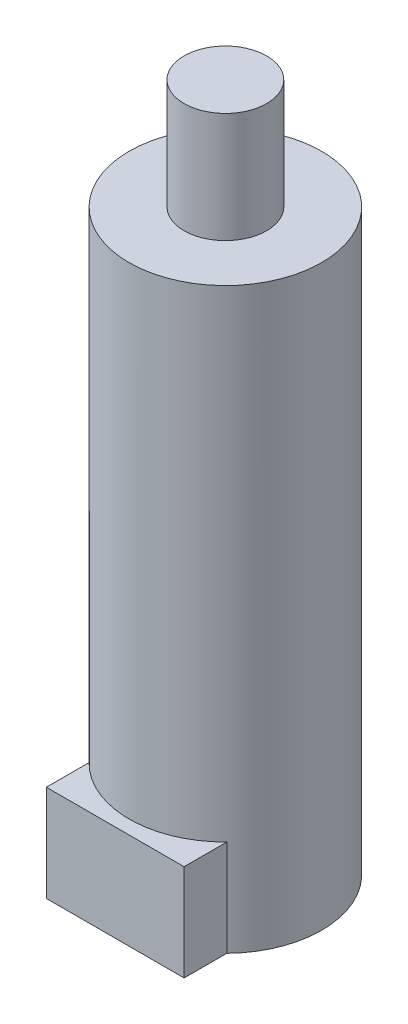
SolidWorks part; units mm, degrees
ref_plane "Front Plane" through (0, 0, 0) normal (0, 0, 1) x (1, 0, 0)
ref_plane "Top Plane" through (0, 0, 0) normal (0, 1, 0) x (1, 0, 0)
ref_plane "Right Plane" through (0, 0, 0) normal (1, 0, 0) x (0, 0, -1)
sketch "Sketch1" plane through (0, 0, 0) normal (0, 1, 0) x (1, 0, 0)
  circle A0 centre (0, 0) radius 11.1125
  dimension "D1" = 22.225
extrude "Boss-Extrude1" add sketch "Sketch1" along normal blind 66.675
sketch "Sketch2" plane through (0, 0, 0) normal (0, 0, 1) x (1, 0, 0)
  line L5 (-11.1125, 0) -> (11.1125, 0) construction
  line L6 (-7.9375, 0) -> (7.9375, 0)
  line L7 (-7.9375, 0) -> (-7.9375, 11.1125)
  line L8 (-7.9375, 11.1125) -> (7.9375, 11.1125)
  line L9 (7.9375, 0) -> (7.9375, 11.1125)
  point P7 (0, 11.1125)
  dimension "D1" = 11.1125
  dimension "D2" = 15.875
extrude "Boss-Extrude2" add sketch "Sketch2" along normal blind 12.7
sketch "Sketch3" plane through (0, 66.675, 0) normal (0, 1, 0) x (1, 0, 0)
  circle A0 centre (0, 0) radius 4.7625
  dimension "D1" = 9.525
extrude "Boss-Extrude3" add sketch "Sketch3" along normal blind 12.7
ref_axis "Axis1" through (0, 66.675, 0) along (0, -1, 0)
